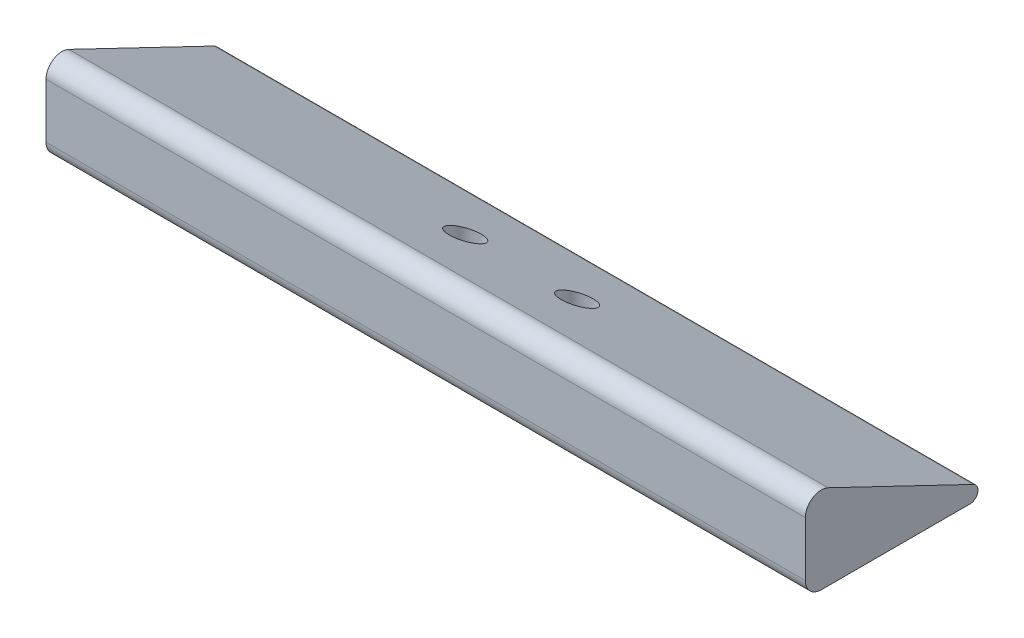
SolidWorks part; units mm, degrees
material "Rubber"
ref_plane "Front Plane" through (0, 0, 0) normal (0, 0, 1) x (1, 0, 0)
ref_plane "Top Plane" through (0, 0, 0) normal (0, 1, 0) x (1, 0, 0)
ref_plane "Right Plane" through (0, 0, 0) normal (1, 0, 0) x (0, 0, -1)
sketch "Sketch1" plane through (0, 0, 0) normal (1, 0, 0) x (0, 0, -1)
  line L0 (2, 0) -> (20.6058, 0)
  line L1 (21.0385, 1.9015) -> (2.8655, 10.6246)
  line L2 (0, 8.8215) -> (0, 2)
  arc A0 (0, 8.8215) -> (2.8655, 10.6246) centre (2, 8.8215) cw
  arc A1 (2, 0) -> (0, 2) centre (2, 2) cw
  arc A2 (21.0385, 1.9015) -> (20.6058, 0) centre (20.6058, 1) cw
  point P6 (0, 12)
  point P9 (0, 0)
  point P12 (25, 0)
  dimension "D1" = 12
  dimension "D3" = 2
  dimension "D4" = 1
  dimension "D2" = 25
extrude "Boss-Extrude1" add sketch "Sketch1" along normal blind 95
ref_plane "Plane1" through (0, 10, 0) normal (0, 1, 0) x (1, 0, 0)
sketch "Sketch2" plane through (0, 10, 0) normal (0, 1, 0) x (1, 0, 0)
  line L0 (95, 11.952) -> (0, 11.952) construction
  line L1 (95, 21.0385) -> (95, 2.8655) construction
  line L2 (0, 21.0385) -> (0, 2.8655) construction
  line L3 (47.5, 11.952) -> (47.5, 18.9766) construction
  circle A0 centre (40.5, 11.952) radius 2
  circle A1 centre (54.5, 11.952) radius 2
  dimension "D1" = 4
  dimension "D2" = 7
extrude "Cut-Extrude1" cut sketch "Sketch2" against normal blind 8
sketch "Sketch3" plane through (0, 2, 0) normal (0, 1, 0) x (1, 0, 0)
  circle A0 centre (40.5, 11.952) radius 1.5
  circle A1 centre (54.5, 11.952) radius 1.5
  dimension "D1" = 3
extrude "Cut-Extrude2" cut sketch "Sketch3" against normal through all
sketch "Sketch4" [suppressed] plane through (0, 0, 0) normal (1, 0, 0) x (0, 0, -1)
  line L0 (0, 1) -> (0, 10.4108)
  line L1 (1.4327, 11.3123) -> (21.0385, 1.9015)
  line L2 (20.6058, 0) -> (1, 0)
  arc A0 (20.6058, 0) -> (21.0385, 1.9015) centre (20.6058, 1) ccw
  arc A1 (1, 0) -> (0, 1) centre (1, 1) cw
  arc A2 (1.4327, 11.3123) -> (0, 10.4108) centre (1, 10.4108) ccw
  point P6 (25, 0)
  point P9 (0, 0)
  point P12 (0, 12)
  dimension "D3" = 1
  dimension "D1" = 25
  dimension "D2" = 12
extrude "Boss-Extrude2" [suppressed] add sketch "Sketch4" along normal blind 40
ref_plane "Plane2" [suppressed] through (0, 10, 0) normal (0, -1, 0) x (-1, 0, 0)
sketch "Sketch5" [suppressed] plane through (0, 10, 0) normal (0, -1, 0) x (-1, 0, 0)
  line L0 (-15, 0) -> (-15, 21.6058) construction
  line L1 (-30, 0) -> (0, 0) construction
  line L2 (0, 21.6058) -> (-30, 21.6058) construction
  line L3 (-15, 10.8029) -> (-8, 10.8029) construction
  circle A0 centre (-8, 10.8029) radius 2
  circle A1 centre (-22, 10.8029) radius 2
  dimension "D1" = 4
  dimension "D2" = 14
extrude "Cut-Extrude4" [suppressed] cut sketch "Sketch5" along normal blind 8
sketch "Sketch6" [suppressed] plane through (0, 2, 0) normal (0, 1, 0) x (1, 0, 0)
  circle A0 centre (8, 10.8029) radius 1.5
  circle A1 centre (22, 10.8029) radius 1.5
  dimension "D1" = 3
extrude "Cut-Extrude5" [suppressed] cut sketch "Sketch6" against normal blind 8
